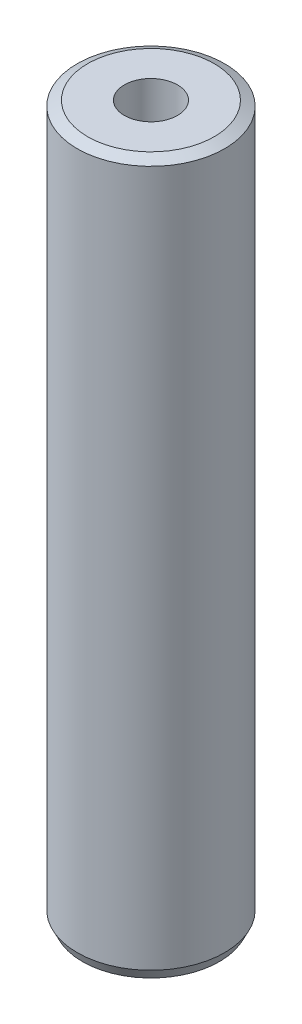
SolidWorks part; units mm, degrees
ref_plane "Front Plane" through (0, 0, 0) normal (0, 0, 1) x (1, 0, 0)
ref_plane "Top Plane" through (0, 0, 0) normal (0, 1, 0) x (1, 0, 0)
ref_plane "Right Plane" through (0, 0, 0) normal (1, 0, 0) x (0, 0, -1)
sketch "Sketch1" plane through (0, 0, 0) normal (0, 1, 0) x (1, 0, 0)
  circle A0 centre (0, 0) radius 57.5
  dimension "SHAFT_OD" = 115
extrude "Boss-Extrude1" add sketch "Sketch1" along normal blind 555.3102
sketch "Sketch2" plane through (0, 0, 0) normal (0, 1, 0) x (1, 0, 0)
  circle A0 centre (0, 0) radius 20.7203
  dimension "BORE_D" = 41.4406
extrude "Cut-Extrude1" cut sketch "Sketch2" along normal through all
chamfer "Chamfer1" distance 4.059 angle 63.405 2 edges at (0, 555.3102, 57.5) (0, 0, 57.5) first distance on face at (0, 555.3102, 57.5) first distance on face at (0, 0, 20.7203)
